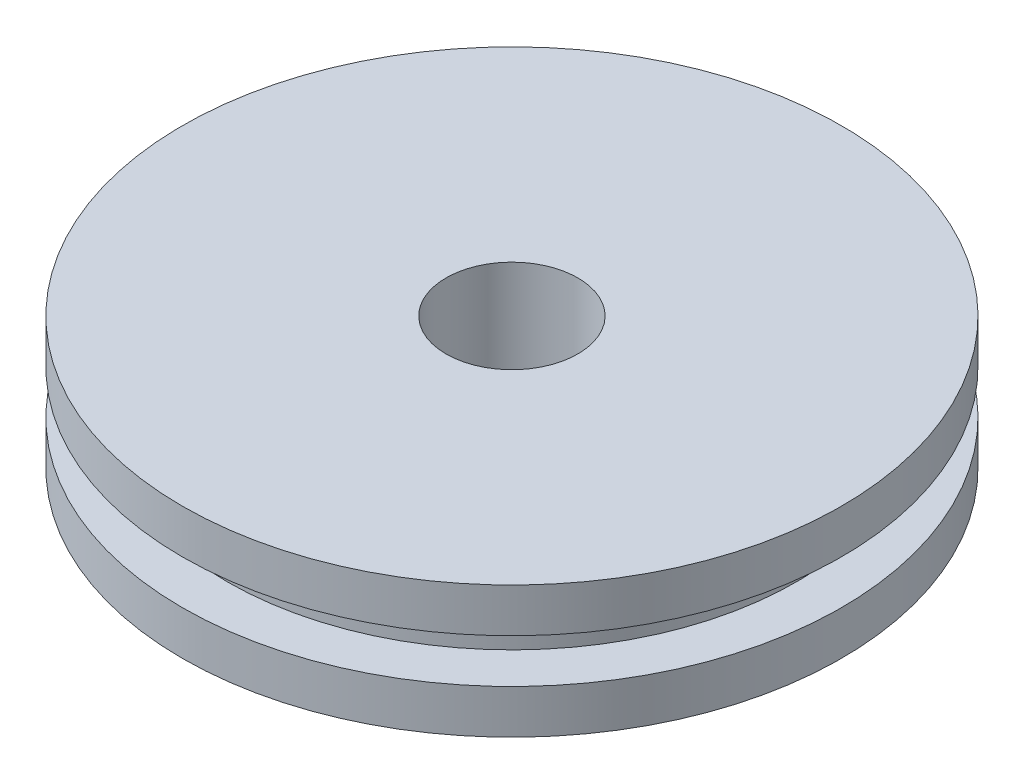
SolidWorks part; units mm, degrees
ref_plane "Front Plane" through (0, 0, 0) normal (0, 0, 1) x (1, 0, 0)
ref_plane "Top Plane" through (0, 0, 0) normal (0, 1, 0) x (1, 0, 0)
ref_plane "Right Plane" through (0, 0, 0) normal (1, 0, 0) x (0, 0, -1)
sketch "Sketch1" plane through (0, 0, 0) normal (0, 1, 0) x (1, 0, 0)
  circle A0 centre (0, 0) radius 15.875
  dimension "D1" = 31.75
extrude "Boss-Extrude1" add sketch "Sketch1" along normal blind 2.1167
sketch "Sketch2" plane through (0, 2.1167, 0) normal (0, 1, 0) x (1, 0, 0)
  circle A0 centre (0, 0) radius 13.716
  dimension "D1" = 27.432
extrude "Boss-Extrude2" add sketch "Sketch2" along normal blind 2.1167
sketch "Sketch3" plane through (0, 4.2333, 0) normal (0, 1, 0) x (1, 0, 0)
  circle A0 centre (0, 0) radius 15.875
  dimension "D1" = 31.75
extrude "Boss-Extrude3" add sketch "Sketch3" along normal blind 2.1167
sketch "Sketch4" plane through (0, 6.35, 0) normal (0, 1, 0) x (1, 0, 0)
  circle A0 centre (0, 0) radius 3.175
  dimension "D1" = 6.35
sketch "Sketch6" plane through (0, 6.35, 0) normal (0, 1, 0) x (1, 0, 0)
  circle A0 centre (0, 0) radius 3.175
  dimension "D1" = 6.35
extrude "Cut-Extrude2" cut sketch "Sketch6" against normal through all
